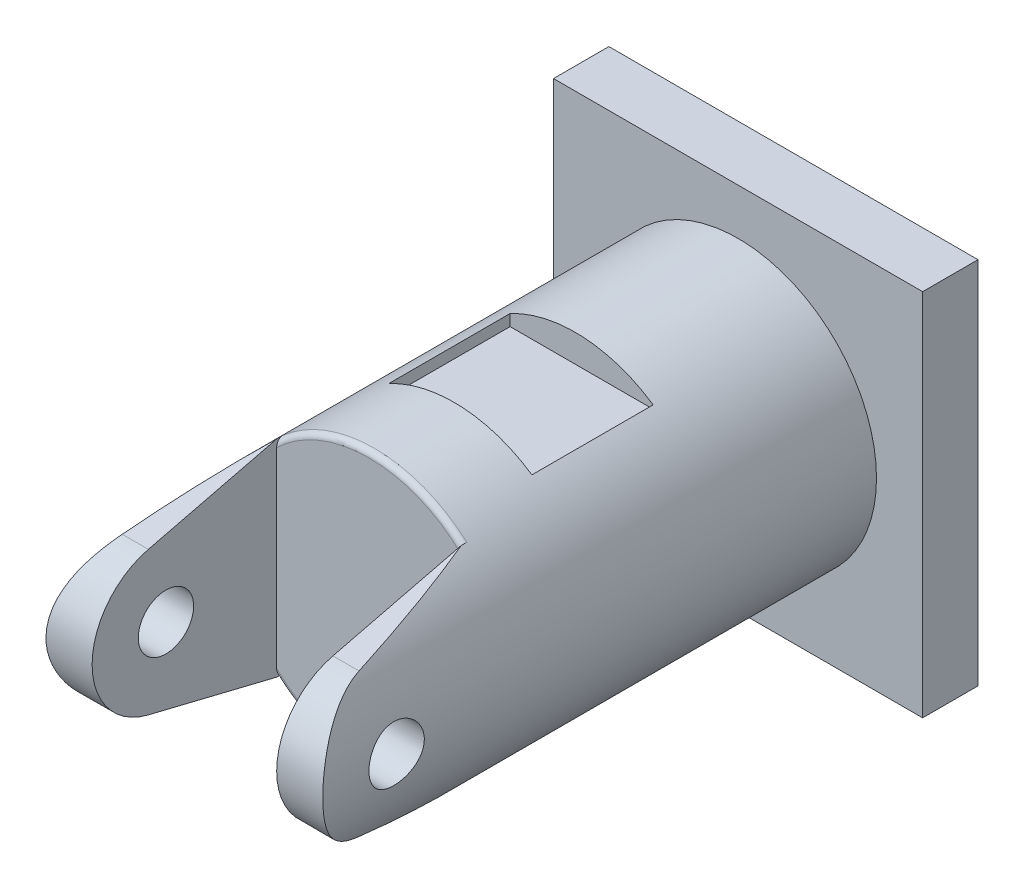
SolidWorks part; units mm, degrees
ref_plane "Alzado" through (0, 0, 0) normal (0, 0, 1) x (1, 0, 0)
ref_plane "Planta" through (0, 0, 0) normal (0, 1, 0) x (1, 0, 0)
ref_plane "Vista lateral" through (0, 0, 0) normal (1, 0, 0) x (0, 0, -1)
sketch "Croquis1" plane through (0, 0, 0) normal (0, 0, 1) x (1, 0, 0)
  circle A1 centre (0, 0) radius 7.5
  dimension "D1" = 15
extrude "Saliente-Extruir1" add sketch "Croquis1" along normal blind 30
sketch "Croquis2" plane through (0, 0, 30) normal (0, 0, 1) x (1, 0, 0)
  line L1 (-5, 7.7396) -> (5, 7.7396)
  line L2 (-5, 7.7396) -> (-5, -7.7396)
  line L3 (-5, -7.7396) -> (5, -7.7396)
  line L4 (5, 7.7396) -> (5, -7.7396)
  line L5 (-5, 7.7396) -> (5, -7.7396) construction
  line L6 (-5, -7.7396) -> (5, 7.7396) construction
  point P0 (0, 0)
  dimension "D1" = 10
extrude "Cortar-Extruir1" cut sketch "Croquis2" against normal blind 10 and the other way through all
sketch "Croquis3" plane through (0, 0, 0) normal (1, 0, 0) x (0, 0, -1)
  line L0 (-20, 7.5) -> (-20, 5.5902)
  line L1 (-20, 5.5902) -> (-26.9529, 3.8847)
  line L2 (-20, -7.5) -> (-20, -5.5902)
  line L3 (-20, -5.5902) -> (-26.9527, -3.885)
  line L4 (-30, 5.5902) -> (-30, -5.5902) construction
  line L5 (-20, -5.5902) -> (-30, -5.5902) construction
  arc A0 (-26.9529, 3.8847) -> (-26.9527, -3.885) centre (-26, -0.0002) ccw
  dimension "D1" = 4
  dimension "D2" = 5.59
extrude "Cortar-Extruir3" cut sketch "Croquis3" against normal through all both and the other way through all
sketch "Croquis4" plane through (0, 0, 0) normal (1, 0, 0) x (0, 0, -1)
  circle A0 centre (-26, -0.0002) radius 1.5
  arc A1 (-26.9529, 3.8847) -> (-26.9527, -3.885) centre (-26, -0.0002) ccw construction
  dimension "D1" = 3
extrude "Cortar-Extruir4" cut sketch "Croquis4" against normal through all both and the other way through all
fillet "Redondeo1" radius 0.3 2 edges at (0, 7.5, 20) (0, -7.5, 20)
sketch "Croquis5" plane through (0, 0, 0) normal (0, 0, -1) x (-1, 0, 0)
  line L1 (-10, 10) -> (10, 10)
  line L2 (-10, 10) -> (-10, -10)
  line L3 (-10, -10) -> (10, -10)
  line L4 (10, 10) -> (10, -10)
  line L5 (-10, 10) -> (10, -10) construction
  line L6 (-10, -10) -> (10, 10) construction
  point P0 (0, 0)
  dimension "D1" = 20
  dimension "D2" = 20
extrude "Saliente-Extruir2" add sketch "Croquis5" along normal blind 3
sketch "Croquis6" plane through (0, 0, 0) normal (0, 1, 0) x (1, 0, 0)
  line L1 (-3.5354, -8.817) -> (4.2148, -8.817)
  line L2 (-3.5354, -8.817) -> (-3.5354, -15.3862)
  line L3 (-3.5354, -15.3862) -> (4.2148, -15.3862)
  line L4 (4.2148, -8.817) -> (4.2148, -15.3862)
extrude "Cortar-Extruir5" cut sketch "Croquis6" along normal blind 10 from offset 6
